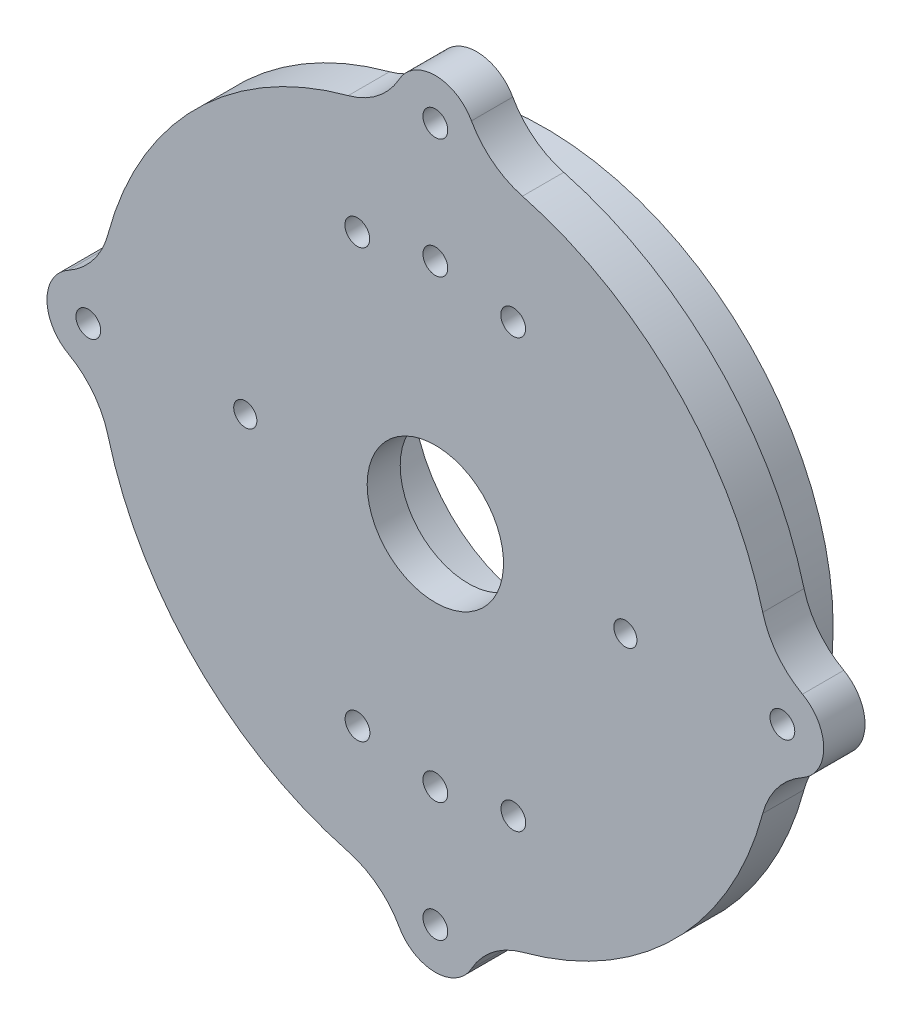
SolidWorks part; units mm, degrees
ref_plane "Ön Düzlem" through (0, 0, 0) normal (0, 0, 1) x (1, 0, 0)
ref_plane "Üst Düzlem" through (0, 0, 0) normal (0, 1, 0) x (1, 0, 0)
ref_plane "Sağ Düzlem" through (0, 0, 0) normal (1, 0, 0) x (0, 0, -1)
sketch "Çizim1" plane through (0, 0, 0) normal (0, 0, 1) x (1, 0, 0)
  circle A0 centre (0, 0) radius 16.1
  circle A1 centre (0, 0) radius 22.5
  circle A2 centre (0, 0) radius 34.9
  circle A3 centre (0, 0) radius 31
  dimension "D1" = 32.2
  dimension "D2" = 45
  dimension "D3" = 69.8
  dimension "D4" = 62
extrude "Yükseklik-Ekstrüzyon1" add sketch "Çizim1" along normal blind 8.25 contours A1 A0 | A2 A3 region at (-21.8636, 0, 0) region at (-33.9129, 0, 0)
sketch "Çizim2" plane through (0, 0, 8.25) normal (0, 0, 1) x (1, 0, 0)
  arc A6 (-10.5408, 39.6218) -> (-39.6218, 10.5408) centre (0, 0) ccw
  circle A7 centre (0, 42) radius 1.5
  arc A8 (4.3706, 44.4286) -> (-4.3706, 44.4286) centre (0, 42) ccw
  arc A9 (-4.3706, 44.4286) -> (-10.5408, 39.6218) centre (-13.1118, 49.2857) cw
  arc A10 (4.3706, 44.4286) -> (10.5408, 39.6218) centre (13.1118, 49.2857) ccw
  arc A11 (44.4286, 4.3706) -> (39.6218, 10.5408) centre (49.2857, 13.1118) cw
  arc A12 (44.4286, -4.3706) -> (44.4286, 4.3706) centre (42, 0) ccw
  circle A13 centre (42, 0) radius 1.5
  arc A14 (44.4286, -4.3706) -> (39.6218, -10.5408) centre (49.2857, -13.1118) ccw
  arc A15 (4.3706, -44.4286) -> (10.5408, -39.6218) centre (13.1118, -49.2857) cw
  arc A16 (-4.3706, -44.4286) -> (4.3706, -44.4286) centre (0, -42) ccw
  circle A17 centre (0, -42) radius 1.5
  arc A18 (-4.3706, -44.4286) -> (-10.5408, -39.6218) centre (-13.1118, -49.2857) ccw
  arc A19 (-44.4286, -4.3706) -> (-39.6218, -10.5408) centre (-49.2857, -13.1118) cw
  arc A20 (-44.4286, 4.3706) -> (-44.4286, -4.3706) centre (-42, 0) ccw
  circle A21 centre (-42, 0) radius 1.5
  arc A22 (-44.4286, 4.3706) -> (-39.6218, 10.5408) centre (-49.2857, 13.1118) ccw
  arc A23 (-39.6218, -10.5408) -> (-10.5408, -39.6218) centre (0, 0) ccw
  arc A24 (10.5408, -39.6218) -> (39.6218, -10.5408) centre (0, 0) ccw
  arc A25 (39.6218, 10.5408) -> (10.5408, 39.6218) centre (0, 0) ccw
  circle A26 centre (0, 0) radius 7.15
  point P0 (0, 0)
  point P17 (0, 0)
  point P48 (0, 0)
  dimension "D1" = 82
  dimension "D2" = 42
  dimension "D7" = 10
  dimension "D8" = 3
  dimension "D9" = 10
  dimension "D10" = 10
  dimension "D12" = 14.3
  dimension "D11" = 4
extrude "Yükseklik-Ekstrüzyon2" add sketch "Çizim2" along normal blind 5
sketch "Çizim7" plane through (0, 0, 8.25) normal (0, 0, -1) x (-1, 0, 0)
  circle A0 centre (0, 0) radius 16.1 construction
  circle A1 centre (0, 0) radius 16.1
extrude "Kes-Ekstrüzyon2" cut sketch "Çizim7" against normal blind 1
sketch "Çizim8" plane through (0, 0, 9.25) normal (0, 0, -1) x (-1, 0, 0)
  circle A0 centre (0, 0) radius 8.25
  dimension "D1" = 16.5
extrude "Kes-Ekstrüzyon3" cut sketch "Çizim8" against normal up to surface (4 mm away) up to face at (0, 0, 13.25)
sketch "Çizim9" plane through (0, 0, 13.25) normal (0, 0, 1) x (1, 0, 0)
  circle A0 centre (-23, 0) radius 1.4
  circle A1 centre (23, 0) radius 1.4
  dimension "D1" = 2.8
  dimension "D2" = 2.8
  dimension "D4" = 23
  dimension "D3" = 46
extrude "Kes-Ekstrüzyon4" cut sketch "Çizim9" against normal blind 25.4 contours A0 | A1
sketch "Çizim10" plane through (0, 0, 8.25) normal (0, 0, -1) x (-1, 0, 0)
  circle A0 centre (0, 27.5431) radius 1.5
  circle A1 centre (9.4433, 25.8737) radius 1.5
  circle A2 centre (-9.4203, 25.882) radius 1.5
  circle A3 centre (9.4203, -25.882) radius 1.5
  circle A4 centre (0, -27.5431) radius 1.5
  circle A5 centre (-9.4433, -25.8737) radius 1.5
  point P2 (-23.6405, -23.8521)
  point P8 (0, 0)
  point P11 (0, 0)
  point P16 (0, 0)
  point P17 (0, 0)
  point P18 (0, 0)
  dimension "D1" = 3
  dimension "D2" = 2
  dimension "D3" = 2
  dimension "D4" = 9.4203
  dimension "D5" = 9.4433
  dimension "D6" = 27.5431
  dimension "D7" = 2
extrude "Kes-Ekstrüzyon5" cut sketch "Çizim10" against normal up to surface (5 mm away) up to face at (-21.6, 0, 13.25)
